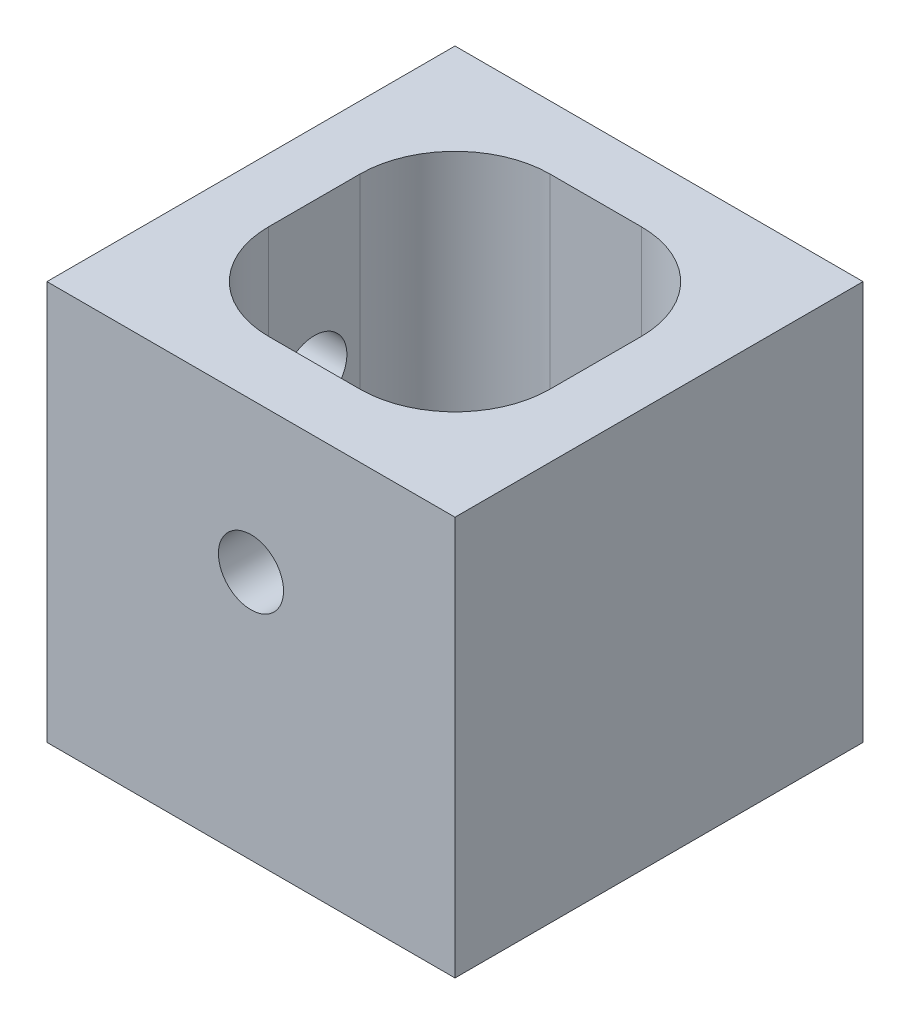
SolidWorks part; units mm, degrees
note: '?' marks a value the reader was unsure of.
material "6061-T6 (SS)"
ref_plane "Front Plane" through (0, 0, 0) normal (0, 0, 1) x (1, 0, 0)
ref_plane "Top Plane" through (0, 0, 0) normal (0, 1, 0) x (1, 0, 0)
ref_plane "Right Plane" through (0, 0, 0) normal (1, 0, 0) x (0, 0, -1)
sketch "Sketch1" plane through (0, 0, 0) normal (0, 1, 0) x (1, 0, 0)
  line L1 (-20.45, -20.45) -> (20.45, -20.45)
  line L2 (-20.45, -20.45) -> (-20.45, 20.45)
  line L3 (-20.45, 20.45) -> (20.45, 20.45)
  line L4 (20.45, -20.45) -> (20.45, 20.45)
  line L5 (-20.45, -20.45) -> (20.45, 20.45) construction
  line L6 (-20.45, 20.45) -> (20.45, -20.45) construction
  point P0 (0, 0)
  dimension "D1" = 40.9
extrude "Boss-Extrude1" add sketch "Sketch1" along normal blind 40
ref_plane "Plane1" through (0, 9.525, 0) normal (0, -1, 0) x (-1, 0, 0)
sketch "Sketch3" plane through (0, 40, 0) normal (0, 1, 0) x (1, 0, 0)
  line L0 (-14.1, 14.1) -> (-14.1, 20.45) construction
  line L1 (14.1, -14.1) -> (-14.1, -14.1)
  line L2 (14.1, -14.1) -> (14.1, 14.1)
  line L3 (14.1, 14.1) -> (-14.1, 14.1)
  line L4 (-14.1, -14.1) -> (-14.1, 14.1)
  line L5 (14.1, -14.1) -> (-14.1, 14.1) construction
  line L6 (14.1, 14.1) -> (-14.1, -14.1) construction
  line L7 (20.45, 20.45) -> (-20.45, 20.45) construction
  line L8 (-14.1, 14.1) -> (-20.45, 14.1) construction
  line L9 (-20.45, 20.45) -> (-20.45, -20.45) construction
  point P0 (0, 0)
  dimension "D1" = 6.35
extrude "Cut-Extrude1" cut sketch "Sketch3" against normal up to surface (30.475 mm away)
fillet "Fillet1" radius 9.525 4 edges at (14.1, 24.7625, 14.1) (-14.1, 24.7625, 14.1) (14.1, 24.7625, -14.1) (-14.1, 24.7625, -14.1)
hole_wizard "5/16-18 Tapped Hole1" positions "Sketch5" profile "Sketch4" tap size "5/16-18" standard "ANSI Inch"
sketch "Sketch5" plane through (0, 0, 20.45) normal (0, 0, 1) x (1, 0, 0)
  line L0 (-20.45, 0) -> (20.45, 0) construction
  point P0 (0, 25)
  dimension "D1" = 25
sketch "Sketch4" plane through (0, 25, 20.45) normal (1, 0, 0) x (0, -1, 0)
  line L0 (0, 0) -> (0, 24.8846)
  line L1 (0, 24.8846) -> (3.2639, 22.9235)
  line L2 (3.2639, 22.9235) -> (3.2639, 0)
  line L5 (3.2639, 0) -> (0, 0)
  line L10 (0, 24.8846) -> (-3.2639, 22.9235) construction
  line L11 (0, -6.35) -> (0, 107.95) construction
  dimension "Tap Drill Dia." = 6.5278
  dimension "Tap Drill Depth" = 22.9235
  dimension "Drill Angle" = 118
cosmetic thread "Hole Thread1"
ref_axis "Axis1" through (0, -2, 0) along (0, 1, 0)?
pattern_circular "CirPattern1" count 2 every 90 about axis through (0, -2, 0) along (0, 1, 0) of "5/16-18 Tapped Hole1"
hole_wizard "1/4-20 Tapped Hole1" positions "Sketch7" profile "Sketch6" tap size "1/4-20" standard "ANSI Inch"
sketch "Sketch7" plane through (0, 9.525, 0) normal (0, 1, 0) x (1, 0, 0)
  line L0 (0, 0) -> (0, 50000) construction
  line L1 (-1.9267, 25.4) -> (-50001.9267, 25.4) construction
  line L2 (-2.718, -25.4) -> (-50002.718, -25.4) construction
  line L3 (0, 0) -> (0, 25.4) construction
  line L6 (0, 0) -> (0, -25.4) construction
  line L8 (-9.525, -9.525) -> (9.525, -9.525)
  line L9 (-9.525, -9.525) -> (-9.525, 9.525)
  line L10 (-9.525, 9.525) -> (9.525, 9.525)
  line L11 (9.525, -9.525) -> (9.525, 9.525)
  line L12 (0, 0) -> (0, 9.525) construction
  line L15 (0, 0) -> (-9.525, 0) construction
  line L18 (0, 0) -> (9.525, 0) construction
  line L21 (0, 0) -> (0, -9.525) construction
  point P20 (-9.525, 9.525)
  point P22 (9.525, 9.525)
  point P24 (9.525, -9.525)
  point P26 (-9.525, -9.525)
  dimension "D1" = 50.8
  dimension "D2" = 9.525
sketch "Sketch6" plane through (-9.525, 9.525, -9.525) normal (1, 0, 0) x (0, 0, 1)
  line L0 (0, 0) -> (0, 9.525)
  line L1 (0, 9.525) -> (2.5527, 9.525)
  line L2 (2.5527, 9.525) -> (2.5527, 0)
  line L5 (2.5527, 0) -> (0, 0)
  line L11 (0, -6.35) -> (0, 107.95) construction
  dimension "Thru Tap Drill Dia." = 5.1054
  dimension "Thru Tap Drill Depth" = 9.525
cosmetic thread "Hole Thread2"
cosmetic thread "Hole Thread3"
cosmetic thread "Hole Thread4"
cosmetic thread "Hole Thread5"
